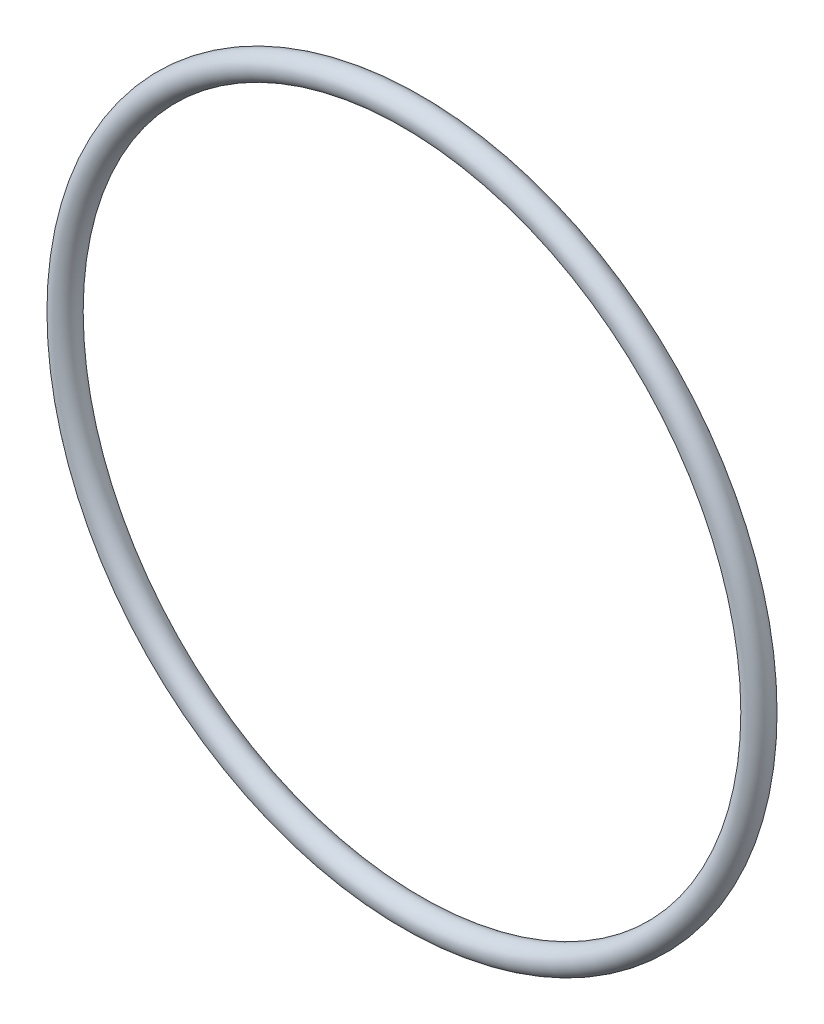
SolidWorks part; units mm, degrees
ref_plane "Front" through (0, 0, 0) normal (0, 0, 1) x (1, 0, 0)
ref_plane "Top" through (0, 0, 0) normal (0, 1, 0) x (1, 0, 0)
ref_plane "Right" through (0, 0, 0) normal (1, 0, 0) x (0, 0, -1)
sketch "Sketch1" plane through (0, 0, 0) normal (0, 0, 1) x (1, 0, 0)
  circle A0 centre (0, 0) radius 46.25
  dimension "d1" = 92.5
sketch "Sketch2" plane through (0, 0, 0) normal (0, 1, 0) x (1, 0, 0)
  circle A0 centre (-48.025, 0) radius 1.775
  point P2 (-46.25, 0)
  dimension "d2" = 3.55
sweep "Sweep1" add profiles "Sketch2" path "Sketch1"
ref_axis "Axis1" through (0, 0, -4.6197) along (0, 0, 1)
